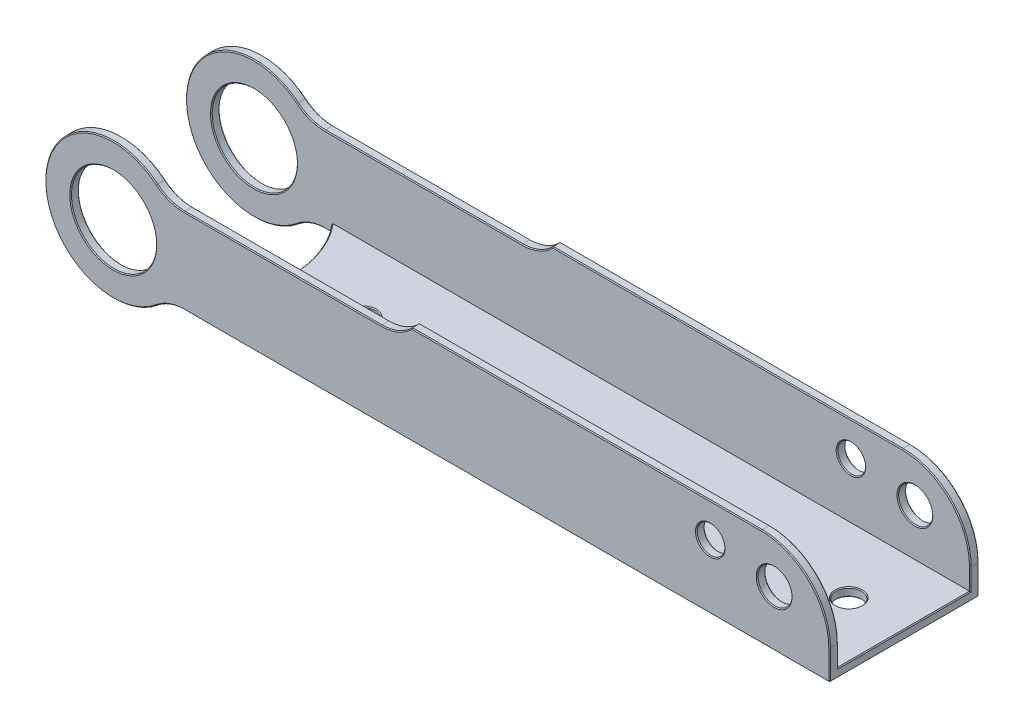
SolidWorks part; units mm, degrees
ref_plane "正面" through (0, 0, 0) normal (0, 0, 1) x (1, 0, 0)
ref_plane "平面" through (0, 0, 0) normal (0, 1, 0) x (1, 0, 0)
ref_plane "右側面" through (0, 0, 0) normal (1, 0, 0) x (0, 0, -1)
sketch "ｽｹｯﾁ1" plane through (0, 0, 0) normal (0, 0, 1) x (1, 0, 0)
  line L1 (12.49, 10) -> (70, 10)
  line L3 (12.49, -10) -> (168, -10)
  line L6 (70, 10) -> (70, 13)
  line L7 (70, 13) -> (168, 13)
  line L8 (168, -10) -> (168, 13)
  arc A0 (12.49, 10) -> (12.49, -10) centre (0, 0) ccw
  point P6 (70, 11.5)
  dimension "D2" = 32
  dimension "D1" = 70
  dimension "D3" = 168
  dimension "D4" = 3
  dimension "D5" = 10
extrude "ﾎﾞｽ - 押し出し1" add sketch "ｽｹｯﾁ1" along normal mid plane 35
fillet "ﾌｨﾚｯﾄ1" radius 16 1 edges at (168, 13, 0)
fillet "ﾌｨﾚｯﾄ2" radius 10 3 edges at (12.49, -10, 0) (12.49, 10, 0) (70, 10, 0)
sketch "ｽｹｯﾁ2" plane through (0, 0, 17.5) normal (0, 0, 1) x (1, 0, 0)
  circle A0 centre (0, 0) radius 10
  dimension "D1" = 20
extrude "ｶｯﾄ - 押し出し1" cut sketch "ｽｹｯﾁ2" against normal through all
sketch "ｽｹｯﾁ3" plane through (0, 0, 0) normal (0, 1, 0) x (1, 0, 0)
  line L5 (-16, 15.5) -> (-16, -15.5)
  line L6 (-16, -15.5) -> (18.3235, -15.5)
  line L7 (-16, 15.5) -> (18.3235, 15.5)
  line L8 (-16, -17.5) -> (10.2235, -17.5) construction
  arc A0 (18.3235, 15.5) -> (18.3235, -15.5) centre (0, 0) cw
  point P4 (-15.7425, 15.5)
  point P10 (-16, 0)
  point P11 (0, 0)
  point P13 (24.1768, 15.5)
  point P14 (0, 0)
  dimension "D3" = 24
  dimension "D1" = 2
extrude "ｶｯﾄ - 押し出し2" cut sketch "ｽｹｯﾁ3" against normal through all both and the other way through all
sketch "ｽｹｯﾁ4" plane through (0, 0, 0) normal (1, 0, 0) x (0, 0, -1)
  line L0 (-17.5, 13) -> (17.5, 13) construction
  line L1 (-15.5, -8) -> (15.5, -8)
  line L2 (-15.5, -8) -> (-15.5, 13)
  line L3 (-15.5, 13) -> (15.5, 13)
  line L4 (15.5, -8) -> (15.5, 13)
  line L5 (-17.5, -10) -> (17.5, -10) construction
  line L6 (15.5, 16) -> (15.5, -16) construction
  line L7 (-15.5, -16) -> (-15.5, 16) construction
  dimension "D1" = 2
extrude "ｶｯﾄ - 押し出し3" cut sketch "ｽｹｯﾁ4" along normal through all
sketch "ｽｹｯﾁ5" plane through (0, 0, 17.5) normal (0, 0, 1) x (1, 0, 0)
  line L0 (16.6132, -10) -> (168, -10) construction
  line L2 (168, -10) -> (168, -3) construction
  circle A0 centre (155, 3) radius 4
  circle A1 centre (140, 5) radius 3.25
  dimension "D1" = 8
  dimension "D2" = 6.5
  dimension "D4" = 15
  dimension "D3" = 13
  dimension "D5" = 13
  dimension "D6" = 28
extrude "ｶｯﾄ - 押し出し4" cut sketch "ｽｹｯﾁ5" against normal through all
sketch "ｽｹｯﾁ6" plane through (0, -10, 0) normal (0, -1, 0) x (1, 0, 0)
  line L0 (168, 17.5) -> (168, -17.5) construction
  circle A0 centre (155, 0) radius 3
  circle A1 centre (41, 0) radius 3
  dimension "D1" = 6
  dimension "D2" = 6
  dimension "D3" = 13
  dimension "D4" = 127
extrude "ｶｯﾄ - 押し出し5" cut sketch "ｽｹｯﾁ6" against normal up to next
chamfer "面取り1" distance 0.2 angle 45 56 edges at (155, -10, -3) (155, -8, 3) (41, -10, -3) (41, -8, 3) (168, -8, 0) (168, -10, 0) (159, 3, 15.5) (159, 3, 17.5) (143.25, 5, 15.5) (143.25, 5, 17.5) (151, 3, -15.5) (159, 3, -17.5) (136.75, 5, -15.5) (143.25, 5, -17.5) (168, -5.5, -15.5) (163.3137, 8.3137, -15.5) (111, 13, -15.5) (17.4684, -10, -15.5) (13.2164, -10.5946, -15.5) (-16, 0, -15.5) (13.2164, 10.5946, -15.5) (66.7316, 10.7805, -15.5) (39.7359, 10, -15.5) (17.4684, -10, 15.5) (13.2164, -10.5946, 15.5) (-16, 0, 15.5) (66.7316, 10.7805, 15.5) (13.2164, 10.5946, 15.5) (39.7359, 10, 15.5) (168, -5.5, 15.5) (163.3137, 8.3137, 15.5) (111, 13, 15.5) (-10, 0, -15.5) (10, 0, 15.5) (10, 0, 17.5) (92.3066, -10, 17.5) (13.2164, -10.5946, 17.5) (-16, 0, 17.5) (66.7316, 10.7805, 17.5) (13.2164, 10.5946, 17.5) (39.7359, 10, 17.5) (168, -6.5, 17.5) (111, 13, 17.5) (163.3137, 8.3137, 17.5) (10, 0, -17.5) (92.3066, -10, -17.5) (13.2164, -10.5946, -17.5) (-16, 0, -17.5) (66.7316, 10.7805, -17.5) (13.2164, 10.5946, -17.5) (39.7359, 10, -17.5) (168, -6.5, -17.5) (163.3137, 8.3137, -17.5) (111, 13, -17.5) (24, -8, 0) (24, -10, 0)
